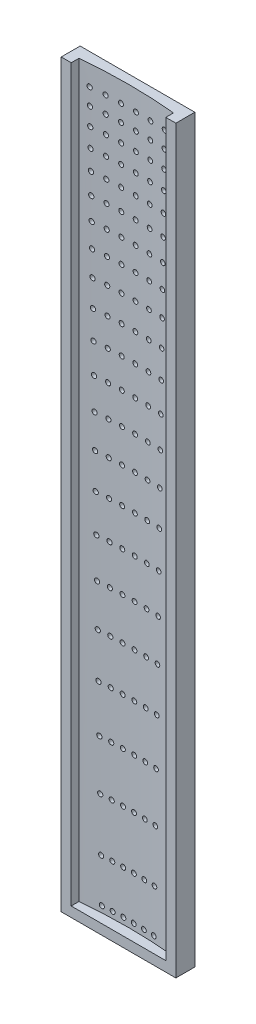
SolidWorks part; units mm, degrees
ref_plane "Front Plane" through (0, 0, 0) normal (0, 0, 1) x (1, 0, 0)
ref_plane "Top Plane" through (0, 0, 0) normal (0, 1, 0) x (1, 0, 0)
ref_plane "Right Plane" through (0, 0, 0) normal (1, 0, 0) x (0, 0, -1)
sketch "Sketch1" plane through (0, 0, 0) normal (0, 0, 1) x (1, 0, 0)
  line L0 (0, 464.91) -> (0, -53.7621) construction
  line L1 (207.2765, 0) -> (-181.268, 0) construction
  line L2 (23.8804, 464.91) -> (23.8804, -53.7621) construction
  line L3 (-23.8804, 464.91) -> (-23.8804, -53.7621) construction
  line L4 (16.5652, 464.91) -> (16.5652, -53.7621) construction
  line L5 (-16.5652, 464.91) -> (-16.5652, -53.7621) construction
  line L6 (-39.4637, 452.8091) -> (40.6786, 452.8091) construction
  line L7 (40.6786, 4) -> (-39.4637, 4) construction
  line L8 (-16.5652, 4) -> (-23.8804, 452.8091) construction
  line L9 (23.8804, 452.8091) -> (16.5652, 4) construction
  line L10 (-39.4637, 442.2134) -> (40.6786, 442.2134) construction
  line L11 (40.6786, 31.6398) -> (-39.4637, 31.6398) construction
  line L12 (40.6786, 430.9875) -> (-39.4637, 430.9875) construction
  line L13 (-16.5652, 4) -> (-9.9352, 4) construction
  line L14 (-39.4637, 65.2793) -> (40.6786, 65.2793) construction
  line L15 (-39.4637, 364.0154) -> (40.6786, 364.0154) construction
  line L17 (-23.8804, 452.8091) -> (-14.3304, 452.8091) construction
  line L18 (-39.4637, 97.0308) -> (40.6786, 97.0308) construction
  line L19 (-23.7077, 442.2134) -> (-14.2277, 442.2134) construction
  line L20 (40.6786, 127.0002) -> (-39.4637, 127.0002) construction
  line L21 (-23.5248, 430.9875) -> (-14.1148, 430.9875) construction
  line L22 (-39.4637, 155.2875) -> (40.6786, 155.2875) construction
  line L23 (-23.3309, 419.0942) -> (-14.0009, 419.0942) construction
  line L24 (40.6786, 181.9872) -> (-39.4637, 181.9872) construction
  line L25 (-23.1255, 406.4936) -> (-13.8755, 406.4936) construction
  line L26 (-39.4637, 207.1884) -> (40.6786, 207.1884) construction
  line L27 (-22.9079, 393.1437) -> (-13.7479, 393.1437) construction
  line L28 (40.6786, 230.9751) -> (-39.4637, 230.9751) construction
  line L29 (-22.6774, 379.0001) -> (-13.6074, 379.0001) construction
  line L30 (-39.4637, 253.4267) -> (40.6786, 253.4267) construction
  line L31 (-22.4332, 364.0154) -> (-13.4632, 364.0154) construction
  line L32 (40.6786, 274.6183) -> (-39.4637, 274.6183) construction
  line L33 (-22.1744, 348.1397) -> (-13.3044, 348.1397) construction
  line L34 (-39.4637, 294.6205) -> (40.6786, 294.6205) construction
  line L35 (-21.9003, 331.3199) -> (-13.1403, 331.3199) construction
  line L36 (40.6786, 313.5) -> (-39.4637, 313.5) construction
  line L37 (-21.6098, 313.5) -> (-12.9698, 313.5) construction
  line L38 (-39.4637, 331.3199) -> (40.6786, 331.3199) construction
  line L40 (40.6786, 348.1397) -> (-39.4637, 348.1397) construction
  line L42 (-39.4637, 379.0001) -> (40.6786, 379.0001) construction
  line L44 (40.6786, 393.1438) -> (-39.4637, 393.1437) construction
  line L46 (-39.4637, 406.4936) -> (40.6786, 406.4936) construction
  line L48 (40.6786, 419.0942) -> (-39.4637, 419.0942) construction
  circle A0 centre (-16.5652, 4) radius 1.575
  circle A1 centre (-9.9352, 4) radius 1.575
  circle A2 centre (-3.3052, 4) radius 1.575
  circle A3 centre (3.3248, 4) radius 1.575
  circle A4 centre (9.9548, 4) radius 1.575
  circle A5 centre (16.5848, 4) radius 1.575
  circle A6 centre (-23.8804, 452.8091) radius 1.575
  circle A7 centre (-14.3304, 452.8091) radius 1.575
  circle A8 centre (-4.7804, 452.8091) radius 1.575
  circle A9 centre (4.7696, 452.8091) radius 1.575
  circle A10 centre (14.3196, 452.8091) radius 1.575
  circle A11 centre (23.8696, 452.8091) radius 1.575
  circle A12 centre (-23.7077, 442.2134) radius 1.575
  circle A13 centre (-14.2277, 442.2134) radius 1.575
  circle A14 centre (-4.7477, 442.2134) radius 1.575
  circle A15 centre (4.7323, 442.2134) radius 1.575
  circle A16 centre (14.2123, 442.2134) radius 1.575
  circle A17 centre (23.6923, 442.2134) radius 1.575
  circle A18 centre (-23.5248, 430.9875) radius 1.575
  circle A19 centre (-14.1148, 430.9875) radius 1.575
  circle A20 centre (-4.7048, 430.9875) radius 1.575
  circle A21 centre (4.7052, 430.9875) radius 1.575
  circle A22 centre (14.1152, 430.9875) radius 1.575
  circle A23 centre (23.5252, 430.9875) radius 1.575
  circle A24 centre (-23.3309, 419.0942) radius 1.575
  circle A25 centre (-14.0009, 419.0942) radius 1.575
  circle A26 centre (-4.6709, 419.0942) radius 1.575
  circle A27 centre (4.6591, 419.0942) radius 1.575
  circle A28 centre (13.9891, 419.0942) radius 1.575
  circle A29 centre (23.3191, 419.0942) radius 1.575
  circle A30 centre (-23.1255, 406.4936) radius 1.575
  circle A31 centre (-13.8755, 406.4936) radius 1.575
  circle A32 centre (-4.6255, 406.4936) radius 1.575
  circle A33 centre (4.6245, 406.4936) radius 1.575
  circle A34 centre (13.8745, 406.4936) radius 1.575
  circle A35 centre (23.1245, 406.4936) radius 1.575
  circle A36 centre (-22.9079, 393.1437) radius 1.575
  circle A37 centre (-13.7479, 393.1437) radius 1.575
  circle A38 centre (-4.5879, 393.1437) radius 1.575
  circle A39 centre (4.5721, 393.1437) radius 1.575
  circle A40 centre (13.7321, 393.1437) radius 1.575
  circle A41 centre (22.8921, 393.1437) radius 1.575
  circle A42 centre (-22.6774, 379.0001) radius 1.575
  circle A43 centre (-13.6074, 379.0001) radius 1.575
  circle A44 centre (-4.5374, 379.0001) radius 1.575
  circle A45 centre (4.5326, 379.0001) radius 1.575
  circle A46 centre (13.6026, 379.0001) radius 1.575
  circle A47 centre (22.6726, 379.0001) radius 1.575
  circle A48 centre (-22.4332, 364.0154) radius 1.575
  circle A49 centre (-13.4632, 364.0154) radius 1.575
  circle A50 centre (-4.4932, 364.0154) radius 1.575
  circle A51 centre (4.4768, 364.0154) radius 1.575
  circle A52 centre (13.4468, 364.0154) radius 1.575
  circle A53 centre (22.4168, 364.0154) radius 1.575
  circle A54 centre (-22.1744, 348.1397) radius 1.575
  circle A55 centre (-13.3044, 348.1397) radius 1.575
  circle A56 centre (-4.4344, 348.1397) radius 1.575
  circle A57 centre (4.4356, 348.1397) radius 1.575
  circle A58 centre (13.3056, 348.1397) radius 1.575
  circle A59 centre (22.1756, 348.1397) radius 1.575
  circle A60 centre (-21.9003, 331.3199) radius 1.575
  circle A61 centre (-13.1403, 331.3199) radius 1.575
  circle A62 centre (-4.3803, 331.3199) radius 1.575
  circle A63 centre (4.3797, 331.3199) radius 1.575
  circle A64 centre (13.1397, 331.3199) radius 1.575
  circle A65 centre (21.8997, 331.3199) radius 1.575
  circle A66 centre (-21.6098, 313.5) radius 1.575
  circle A67 centre (-12.9698, 313.5) radius 1.575
  circle A68 centre (-4.3298, 313.5) radius 1.575
  circle A69 centre (4.3102, 313.5) radius 1.575
  circle A70 centre (12.9502, 313.5) radius 1.575
  circle A71 centre (21.5902, 313.5) radius 1.575
  circle A72 centre (-21.3021, 294.6205) radius 1.575
  circle A73 centre (-12.7812, 294.6205) radius 1.575
  circle A74 centre (-4.2604, 294.6205) radius 1.575
  circle A75 centre (4.2604, 294.6205) radius 1.575
  circle A76 centre (12.7813, 294.6205) radius 1.575
  circle A77 centre (21.3021, 294.6205) radius 1.575
  circle A78 centre (-20.9761, 274.6183) radius 1.575
  circle A79 centre (-12.5856, 274.6183) radius 1.575
  circle A80 centre (-4.1952, 274.6183) radius 1.575
  circle A81 centre (4.1952, 274.6183) radius 1.575
  circle A82 centre (12.5856, 274.6183) radius 1.575
  circle A83 centre (20.9761, 274.6183) radius 1.575
  circle A84 centre (-20.6307, 253.4267) radius 1.575
  circle A85 centre (-12.3784, 253.4267) radius 1.575
  circle A86 centre (-4.1261, 253.4267) radius 1.575
  circle A87 centre (4.1261, 253.4267) radius 1.575
  circle A88 centre (12.3784, 253.4267) radius 1.575
  circle A89 centre (20.6307, 253.4267) radius 1.575
  circle A90 centre (-20.2647, 230.9751) radius 1.575
  circle A91 centre (-12.1588, 230.9751) radius 1.575
  circle A92 centre (-4.0529, 230.9751) radius 1.575
  circle A93 centre (4.0529, 230.9751) radius 1.575
  circle A94 centre (12.1588, 230.9751) radius 1.575
  circle A95 centre (20.2647, 230.9751) radius 1.575
  circle A96 centre (-19.877, 207.1884) radius 1.575
  circle A97 centre (-11.9262, 207.1884) radius 1.575
  circle A98 centre (-3.9754, 207.1884) radius 1.575
  circle A99 centre (3.9754, 207.1884) radius 1.575
  circle A100 centre (11.9262, 207.1884) radius 1.575
  circle A101 centre (19.877, 207.1884) radius 1.575
  circle A102 centre (-19.4662, 181.9872) radius 1.575
  circle A103 centre (-11.6797, 181.9872) radius 1.575
  circle A104 centre (-3.8933, 181.9872) radius 1.575
  circle A105 centre (3.8932, 181.9872) radius 1.575
  circle A106 centre (11.6797, 181.9872) radius 1.575
  circle A107 centre (19.4662, 181.9872) radius 1.575
  circle A108 centre (-19.0311, 155.2875) radius 1.575
  circle A109 centre (-11.4186, 155.2875) radius 1.575
  circle A110 centre (-3.8062, 155.2875) radius 1.575
  circle A111 centre (3.8062, 155.2875) radius 1.575
  circle A112 centre (11.4186, 155.2875) radius 1.575
  circle A113 centre (19.0311, 155.2875) radius 1.575
  circle A114 centre (-18.57, 127.0002) radius 1.575
  circle A115 centre (-11.142, 127.0002) radius 1.575
  circle A116 centre (-3.714, 127.0002) radius 1.575
  circle A117 centre (3.714, 127.0002) radius 1.575
  circle A118 centre (11.142, 127.0002) radius 1.575
  circle A119 centre (18.57, 127.0002) radius 1.575
  circle A120 centre (-18.0815, 97.0308) radius 1.575
  circle A121 centre (-10.8489, 97.0308) radius 1.575
  circle A122 centre (-3.6163, 97.0308) radius 1.575
  circle A123 centre (3.6163, 97.0308) radius 1.575
  circle A124 centre (10.8489, 97.0308) radius 1.575
  circle A125 centre (18.0815, 97.0308) radius 1.575
  circle A126 centre (-17.564, 65.2793) radius 1.575
  circle A127 centre (-10.5384, 65.2793) radius 1.575
  circle A128 centre (-3.5128, 65.2793) radius 1.575
  circle A129 centre (3.5128, 65.2793) radius 1.575
  circle A130 centre (10.5384, 65.2793) radius 1.575
  circle A131 centre (17.564, 65.2793) radius 1.575
  circle A132 centre (-17.0157, 31.6398) radius 1.575
  circle A133 centre (-10.2094, 31.6398) radius 1.575
  circle A134 centre (-3.4031, 31.6398) radius 1.575
  circle A135 centre (3.4031, 31.6398) radius 1.575
  circle A136 centre (10.2094, 31.6398) radius 1.575
  circle A137 centre (17.0157, 31.6398) radius 1.575
  dimension "D7" = 3.15
  dimension "D31" = 3.15
  dimension "D34" = 3.15
  dimension "D37" = 3.15
  dimension "D40" = 3.15
  dimension "D43" = 3.15
  dimension "D46" = 3.15
  dimension "D49" = 3.15
  dimension "D52" = 3.15
  dimension "D55" = 3.15
  dimension "D58" = 3.15
  dimension "D61" = 3.15
  dimension "D64" = 3.15
  dimension "D66" = 3.15
  dimension "D68" = 3.15
  dimension "D69" = 6
  dimension "D70" = 3.15
  dimension "D72" = 3.15
  dimension "D74" = 3.15
  dimension "D76" = 3.15
  dimension "D78" = 3.15
  dimension "D80" = 3.15
  dimension "D82" = 3.15
  dimension "D84" = 3.15
  dimension "D1" = 23.8804
  dimension "D2" = 23.8804
  dimension "D3" = 16.5652
  dimension "D4" = 16.5652
  dimension "D5" = 452.8091
  dimension "D6" = 4
  dimension "D9" = 6.63
  dimension "D10" = 31.6398
  dimension "D11" = 65.2793
  dimension "D12" = 97.0308
  dimension "D13" = 127.0002
  dimension "D14" = 155.2875
  dimension "D15" = 181.9872
  dimension "D16" = 207.1884
  dimension "D17" = 230.9751
  dimension "D18" = 253.4267
  dimension "D19" = 274.6183
  dimension "D20" = 294.6205
  dimension "D21" = 313.5
  dimension "D22" = 331.3199
  dimension "D23" = 348.1397
  dimension "D24" = 442.2134
  dimension "D25" = 430.9875
  dimension "D26" = 419.0942
  dimension "D27" = 406.4936
  dimension "D28" = 393.1438
  dimension "D29" = 379.0001
  dimension "D30" = 364.0154
  dimension "D33" = 9.55
  dimension "D36" = 9.48
  dimension "D39" = 9.41
  dimension "D42" = 9.33
  dimension "D45" = 9.25
  dimension "D48" = 9.16
  dimension "D51" = 9.07
  dimension "D54" = 8.97
  dimension "D57" = 8.87
  dimension "D60" = 8.76
  dimension "D63" = 8.64
  dimension "D8" = 6
  dimension "D32" = 6
  dimension "D35" = 6
  dimension "D38" = 6
  dimension "D41" = 6
  dimension "D44" = 6
  dimension "D47" = 6
  dimension "D50" = 6
  dimension "D53" = 6
  dimension "D56" = 6
  dimension "D59" = 6
  dimension "D62" = 6
  dimension "D65" = 6
  dimension "D67" = 6
  dimension "D71" = 6
  dimension "D73" = 6
  dimension "D75" = 6
  dimension "D77" = 6
  dimension "D79" = 6
  dimension "D81" = 6
  dimension "D83" = 6
  dimension "D85" = 6
sketch "Sketch2" plane through (0, 0, 0) normal (0, 0, 1) x (1, 0, 0)
  line L0 (30.163, 490.1178) -> (30.163, -68.1918) construction
  line L1 (-30.163, 490.1178) -> (-30.163, -68.1918) construction
  line L2 (0, 464.91) -> (0, -53.7621) construction
  line L3 (36.563, -68.1918) -> (36.563, 490.1178) construction
  line L4 (-36.563, 490.1178) -> (-36.563, -68.1918) construction
  line L5 (-36.563, 0) -> (36.563, 0)
  line L6 (207.2765, 0) -> (-181.268, 0) construction
  line L7 (36.563, 0) -> (36.563, 465.7035)
  line L8 (36.563, 465.7035) -> (-36.563, 465.7035)
  line L9 (-36.563, 465.7035) -> (-36.563, 0)
  dimension "D1" = 30.163
  dimension "D2" = 30.163
  dimension "D3" = 6.4
  dimension "D4" = 6.4
extrude "Boss-Extrude1" add sketch "Sketch2" along normal blind 12.8
extrude "Cut-Extrude1" cut sketch "Sketch1" along normal blind 12.8
sketch "Sketch3" plane through (0, 0, 0) normal (0, 1, 0) x (1, 0, 0)
  line L0 (38.7043, 0) -> (-38.1623, 0) construction
  line L1 (39.8582, -6.4) -> (-38.1623, -6.4) construction
  line L2 (-36.563, -12.8) -> (36.563, -12.8) construction
  line L3 (38.7043, -311.2) -> (0, -311.2) construction
  line L4 (30.163, -12.8) -> (30.163, -7.8961)
  line L5 (-30.163, -12.8) -> (-30.163, -7.8961)
  arc A0 (30.163, -7.8961) -> (-30.163, -7.8961) centre (0, -311.2) ccw
  dimension "D1" = 6.4
  dimension "D2" = 304.8
  dimension "D3" = 30.163
  dimension "D4" = 30.163
extrude "Cut-Extrude3" cut sketch "Sketch3" against normal through all and the other way through all flip side to cut
sketch "Sketch4" plane through (0, 0, 0) normal (0, 0, 1) x (1, 0, 0)
  line L1 (-36.563, 0) -> (36.563, 0)
  line L2 (-36.563, 0) -> (-36.563, -6.4)
  line L3 (-36.563, -6.4) -> (36.563, -6.4)
  line L4 (36.563, 0) -> (36.563, -6.4)
  dimension "D1" = 6.4
extrude "Boss-Extrude3" add sketch "Sketch4" along normal blind 12.8
ref_plane "Plane1" through (0, 0, 4) normal (0, 0, 1) x (1, 0, 0)
sketch "Sketch6" plane through (0, 0, 4) normal (0, 0, 1) x (1, 0, 0)
  line L0 (-36.563, 153.6) -> (-44.4958, 153.6)
  line L1 (-36.563, 153.33) -> (-44.4958, 153.33)
  line L3 (-26.2504, 153.6) -> (-36.563, 153.6)
  line L4 (-36.563, 465.7035) -> (-36.563, -6.4) construction
  line L5 (26.2504, 153.6) -> (37.3073, 153.6)
  line L8 (50.0356, 153.6) -> (37.3073, 153.6)
  line L9 (-44.4958, 313.754) -> (-55.2684, 313.754)
  line L10 (28.4771, 313.754) -> (50.0356, 313.754)
  line L11 (-44.4958, 313.754) -> (-28.4771, 313.754)
  line L15 (64.6899, 313.754) -> (50.0356, 313.754)
  line L16 (-26.2031, 153.33) -> (-36.563, 153.33)
  line L17 (26.2031, 153.33) -> (37.3073, 153.33)
  line L18 (50.0356, 153.33) -> (37.3073, 153.33)
  line L19 (-36.563, 153.87) -> (-44.4958, 153.87)
  line L20 (-26.2979, 153.87) -> (-36.563, 153.87)
  line L21 (26.2979, 153.87) -> (37.3073, 153.87)
  line L22 (50.0356, 153.87) -> (37.3073, 153.87)
  line L26 (64.6899, 314.024) -> (50.0356, 314.024)
  line L27 (28.4981, 314.024) -> (50.0356, 314.024)
  line L28 (-44.4958, 314.024) -> (-28.4981, 314.024)
  line L29 (-44.4958, 314.024) -> (-55.2684, 314.024)
  line L30 (64.6899, 313.484) -> (50.0356, 313.484)
  line L31 (28.4561, 313.484) -> (50.0356, 313.484)
  line L32 (-44.4958, 313.484) -> (-28.4561, 313.484)
  line L33 (-44.4958, 313.484) -> (-55.2684, 313.484)
  spline S0 degree 3 poles (26.2504, 153.6) (17.541, 156.75) (30.7338, 161.5743) (25.114, 165.6353) (21.8679, 167.1233) knots 0 0 0 0 0.285982 0.451262 0.451262 0.451262 0.451262
  spline S1 degree 2 poles (0, 170.2276) (11.6288, 169.7474) (21.8679, 167.1233) knots 0 0 0 0.793699 0.793699 0.793699
  spline S2 degree 2 poles (0, 170.2276) (-11.6288, 169.7474) (-21.8679, 167.1233) knots 0 0 0 0.793699 0.793699 0.793699
  spline S3 degree 3 poles (-26.2504, 153.6) (-17.541, 156.75) (-30.7338, 161.5743) (-25.114, 165.6353) (-21.8679, 167.1233) knots 0 0 0 0 0.285982 0.451262 0.451262 0.451262 0.451262
  spline S4 degree 3 poles (28.4771, 313.754) (17.8437, 315.4169) (30.6297, 319.6107) (21.6794, 323.55) (6.8315, 324.3881) (0, 324.4385) knots 0 0 0 0 0.255769 0.406295 0.664788 0.664788 0.664788 0.664788
  spline S5 degree 3 poles (-28.4771, 313.754) (-17.8437, 315.4169) (-30.6297, 319.6107) (-21.6794, 323.55) (-6.8315, 324.3881) (0, 324.4385) knots 0 0 0 0 0.255769 0.406295 0.664788 0.664788 0.664788 0.664788
  spline S6 degree 1 poles (-26.2031, 153.33) (-21.7774, 166.8678) knots 0 0 1 1 construction
  spline S7 degree 1 poles (0, 169.9574) (-21.7774, 166.8678) knots 0 0 1 1 construction
  spline S8 degree 1 poles (0, 169.9574) (21.7774, 166.8678) knots 0 0 1 1 construction
  spline S9 degree 1 poles (26.2031, 153.33) (21.7774, 166.8678) knots 0 0 1 1 construction
  spline S10 degree 3 poles (-26.2031, 153.33) (-25.9936, 153.4058) (-25.5641, 153.5669) (-24.815, 153.8802) (-24.0098, 154.2766) (-23.2559, 154.7565) (-22.5026, 155.4087) (-21.9945, 156.2788) (-22.0848, 157.7076) (-23.3268, 159.2418) (-25.3206, 160.975) (-26.4604, 162.3278) (-26.5432, 163.1944) (-26.273, 163.8785) (-25.6278, 164.6113) (-24.6411, 165.3588) (-23.5666, 165.9875) (-22.5869, 166.4882) (-22.0444, 166.7452) (-21.7774, 166.8678) knots -0.000487 -0.000487 -0.000487 -0.000487 0.006566 0.013618 0.027724 0.041829 0.055934 0.084145 0.112356 0.168778 0.225199 0.281621 0.309831 0.338042 0.366253 0.394464 0.422675 0.43678 0.450885 0.450885 0.450885 0.450885
  spline S11 degree 2 poles (-21.7774, 166.8678) (-11.5835, 169.4777) (0, 169.9574) knots 0.000381 0.000381 0.000381 0.792786 0.792786 0.792786
  spline S12 degree 2 poles (0, 169.9574) (11.5835, 169.4777) (21.7774, 166.8678) knots 0.000381 0.000381 0.000381 0.792786 0.792786 0.792786
  spline S13 degree 3 poles (21.7774, 166.8678) (22.0444, 166.7452) (22.5869, 166.4882) (23.5666, 165.9875) (24.6411, 165.3588) (25.6278, 164.6113) (26.273, 163.8785) (26.5432, 163.1944) (26.4604, 162.3278) (25.3206, 160.975) (23.3268, 159.2418) (22.0848, 157.7076) (21.9945, 156.2788) (22.5026, 155.4087) (23.2559, 154.7565) (24.0098, 154.2766) (24.815, 153.8802) (25.5641, 153.5669) (25.9936, 153.4058) (26.2031, 153.33) knots -0.000487 -0.000487 -0.000487 -0.000487 0.013618 0.027724 0.055934 0.084145 0.112356 0.140567 0.168778 0.225199 0.281621 0.338042 0.366253 0.394464 0.408569 0.422675 0.43678 0.443833 0.450885 0.450885 0.450885 0.450885
  spline S14 degree 1 poles (-26.2979, 153.87) (-21.9584, 167.3788) knots 0 0 1 1 construction
  spline S15 degree 1 poles (0, 170.4979) (-21.9584, 167.3788) knots 0 0 1 1 construction
  spline S16 degree 1 poles (0, 170.4979) (21.9584, 167.3788) knots 0 0 1 1 construction
  spline S17 degree 1 poles (26.2979, 153.87) (21.9584, 167.3788) knots 0 0 1 1 construction
  spline S18 degree 3 poles (-26.2979, 153.87) (-26.0965, 153.9433) (-25.6829, 154.1013) (-24.9703, 154.4034) (-24.2153, 154.7818) (-23.5338, 155.225) (-22.8924, 155.799) (-22.5463, 156.4506) (-22.597, 157.1913) (-23.0443, 158.0191) (-23.7992, 158.875) (-24.7127, 159.7373) (-25.6436, 160.5989) (-26.4488, 161.462) (-27.0053, 162.3526) (-27.098, 163.3193) (-26.7074, 164.2161) (-25.9601, 165.0422) (-24.9017, 165.8349) (-23.787, 166.4827) (-22.7823, 166.9939) (-22.2304, 167.2541) (-21.9584, 167.3788) knots 0.000493 0.000493 0.000493 0.000493 0.007542 0.014591 0.028689 0.042788 0.056886 0.085082 0.113279 0.141475 0.169671 0.197868 0.226064 0.254261 0.282457 0.310653 0.33885 0.367046 0.395243 0.423439 0.437537 0.451635 0.451635 0.451635 0.451635
  spline S19 degree 2 poles (-21.9584, 167.3788) (-11.6741, 170.0171) (0, 170.4979) knots -0.00038 -0.00038 -0.00038 0.794609 0.794609 0.794609
  spline S20 degree 2 poles (0, 170.4979) (11.6741, 170.0171) (21.9584, 167.3788) knots -0.00038 -0.00038 -0.00038 0.794609 0.794609 0.794609
  spline S21 degree 3 poles (21.9584, 167.3788) (22.2304, 167.2541) (22.7823, 166.9939) (23.787, 166.4827) (24.9017, 165.8349) (25.9601, 165.0422) (26.7074, 164.2161) (27.098, 163.3193) (27.0053, 162.3526) (26.4488, 161.462) (25.6436, 160.5989) (24.7127, 159.7373) (23.7992, 158.875) (23.0443, 158.0191) (22.597, 157.1913) (22.5463, 156.4506) (22.8924, 155.799) (23.5338, 155.225) (24.2153, 154.7818) (24.9703, 154.4034) (25.6829, 154.1013) (26.0965, 153.9433) (26.2979, 153.87) knots 0.000493 0.000493 0.000493 0.000493 0.014591 0.028689 0.056886 0.085082 0.113279 0.141475 0.169671 0.197868 0.226064 0.254261 0.282457 0.310653 0.33885 0.367046 0.395243 0.409341 0.423439 0.437537 0.444586 0.451635 0.451635 0.451635 0.451635
  spline S22 degree 1 poles (28.4981, 314.024) (0, 324.7085) knots 0 0 1 1 construction
  spline S23 degree 1 poles (-28.4981, 314.024) (0, 324.7085) knots 0 0 1 1 construction
  spline S24 degree 3 poles (28.4981, 314.024) (28.2915, 314.0564) (27.868, 314.126) (27.1085, 314.2639) (26.2601, 314.4429) (25.4128, 314.6641) (24.4922, 314.9662) (23.711, 315.3532) (23.3152, 315.7831) (23.2617, 316.1021) (23.4271, 316.531) (23.8601, 317.037) (24.6655, 317.741) (25.6405, 318.4552) (26.4509, 319.1617) (26.908, 319.6924) (27.1125, 320.3093) (26.9229, 320.9087) (26.4684, 321.3792) (25.5868, 321.9241) (23.9855, 322.5077) (20.5176, 323.2978) (15.9793, 323.8876) (10.9851, 324.298) (7.1647, 324.5197) (4.0572, 324.6361) (1.6755, 324.6902) (0.5652, 324.7043) (0, 324.7085) knots 0.000167 0.000167 0.000167 0.000167 0.00536 0.010552 0.020937 0.031322 0.041708 0.062478 0.083248 0.104018 0.124788 0.145559 0.166329 0.207869 0.228639 0.249409 0.27018 0.29095 0.31172 0.33249 0.374031 0.415571 0.498652 0.540192 0.581733 0.623273 0.644043 0.664813 0.664813 0.664813 0.664813
  spline S25 degree 3 poles (0, 324.7085) (-0.5652, 324.7043) (-1.6755, 324.6902) (-4.0572, 324.6361) (-7.1647, 324.5197) (-10.9851, 324.298) (-15.9793, 323.8876) (-20.5176, 323.2978) (-23.9855, 322.5077) (-25.5868, 321.9241) (-26.4684, 321.3792) (-26.9229, 320.9087) (-27.1125, 320.3093) (-26.908, 319.6924) (-26.4509, 319.1617) (-25.6405, 318.4552) (-24.6655, 317.741) (-23.8601, 317.037) (-23.4271, 316.531) (-23.2617, 316.1021) (-23.3152, 315.7831) (-23.711, 315.3532) (-24.4922, 314.9662) (-25.4128, 314.6641) (-26.2601, 314.4429) (-27.1085, 314.2639) (-27.868, 314.126) (-28.2915, 314.0564) (-28.4981, 314.024) knots 0.000167 0.000167 0.000167 0.000167 0.020937 0.041708 0.083248 0.124788 0.166329 0.249409 0.29095 0.33249 0.35326 0.374031 0.394801 0.415571 0.436341 0.457111 0.498652 0.519422 0.540192 0.560962 0.581733 0.602503 0.623273 0.633658 0.644043 0.654428 0.659621 0.664813 0.664813 0.664813 0.664813
  spline S26 degree 1 poles (28.4561, 313.484) (0, 324.1685) knots 0 0 1 1 construction
  spline S27 degree 1 poles (-28.4561, 313.484) (0, 324.1685) knots 0 0 1 1 construction
  spline S28 degree 3 poles (28.4561, 313.484) (28.2457, 313.5169) (27.815, 313.5871) (27.0391, 313.7272) (26.168, 313.9097) (25.288, 314.1376) (24.3124, 314.4552) (23.4405, 314.8774) (22.8315, 315.4619) (22.6897, 316.1927) (22.9772, 316.8392) (23.4764, 317.4191) (24.3304, 318.1651) (25.3068, 318.882) (26.0711, 319.5447) (26.4458, 319.9997) (26.5339, 320.3155) (26.4592, 320.5905) (26.1468, 320.9405) (25.3814, 321.419) (23.8531, 321.9837) (20.4461, 322.761) (15.934, 323.3494) (10.9573, 323.7586) (7.1469, 323.9799) (4.0467, 324.0961) (1.6707, 324.1502) (0.5637, 324.1643) (0, 324.1685) knots -0.000166 -0.000166 -0.000166 -0.000166 0.005029 0.010223 0.020613 0.031002 0.041392 0.062171 0.08295 0.103729 0.124508 0.145287 0.166066 0.207624 0.228403 0.249182 0.269961 0.29074 0.311519 0.332298 0.373857 0.415415 0.498531 0.540089 0.581647 0.623205 0.643984 0.664763 0.664763 0.664763 0.664763
  spline S29 degree 3 poles (0, 324.1685) (-0.5637, 324.1643) (-1.6707, 324.1502) (-4.0467, 324.0961) (-7.1469, 323.9799) (-10.9573, 323.7586) (-15.934, 323.3494) (-20.4461, 322.761) (-23.8531, 321.9837) (-25.3814, 321.419) (-26.1468, 320.9405) (-26.4592, 320.5905) (-26.5339, 320.3155) (-26.4458, 319.9997) (-26.0711, 319.5447) (-25.3068, 318.882) (-24.3304, 318.1651) (-23.4764, 317.4191) (-22.9772, 316.8392) (-22.6897, 316.1927) (-22.8315, 315.4619) (-23.4405, 314.8774) (-24.3124, 314.4552) (-25.288, 314.1376) (-26.168, 313.9097) (-27.0391, 313.7272) (-27.815, 313.5871) (-28.2457, 313.5169) (-28.4561, 313.484) knots -0.000166 -0.000166 -0.000166 -0.000166 0.020613 0.041392 0.08295 0.124508 0.166066 0.249182 0.29074 0.332298 0.353077 0.373857 0.394636 0.415415 0.436194 0.456973 0.498531 0.51931 0.540089 0.560868 0.581647 0.602426 0.623205 0.633595 0.643984 0.654374 0.659568 0.664763 0.664763 0.664763 0.664763
  dimension "D1" = 0.27
  dimension "D2" = 0.27
  dimension "D3" = 0.27
  dimension "D4" = 0.27
chamfer "Chamfer5" distance 0.7 angle 45 4 edges at (0, 465.7035, 0) (-36.563, 229.6518, 0) (0, -6.4, 0) (36.563, 229.6518, 0)
